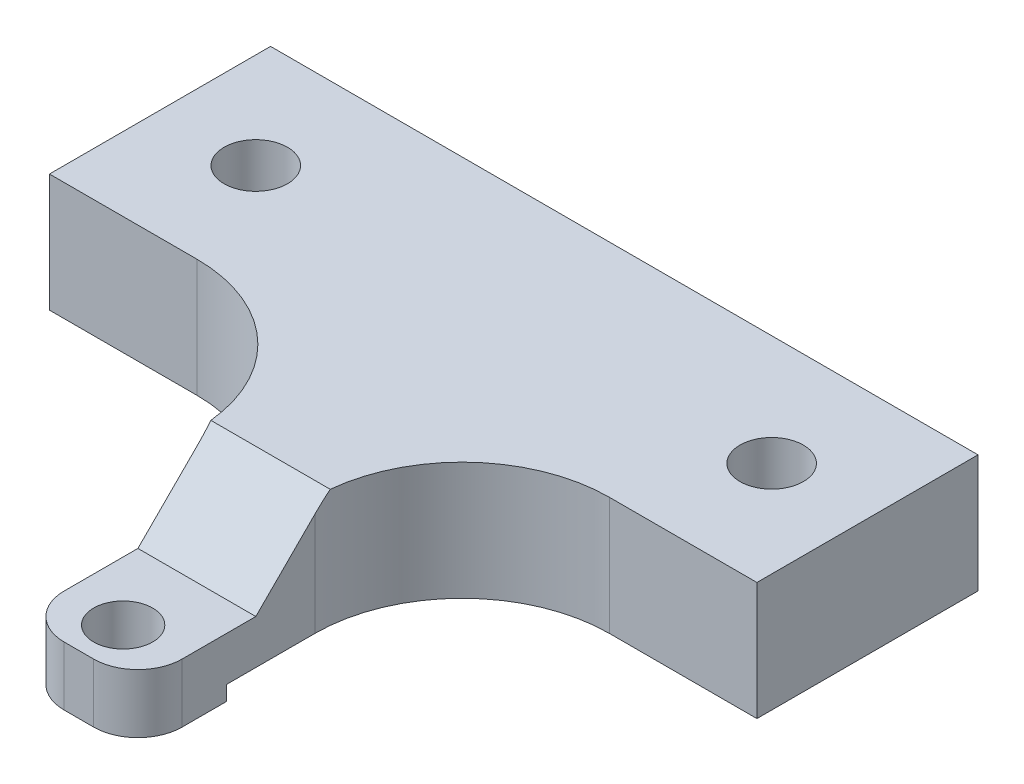
SolidWorks part; units mm, degrees
ref_plane "前视基准面" through (0, 0, 0) normal (0, 0, 1) x (1, 0, 0)
ref_plane "上视基准面" through (0, 0, 0) normal (0, 1, 0) x (1, 0, 0)
ref_plane "右视基准面" through (0, 0, 0) normal (1, 0, 0) x (0, 0, -1)
sketch "草图1" plane through (0, 0, 0) normal (0, 1, 0) x (1, 0, 0)
  line L1 (24, -18.5) -> (-24, -18.5)
  line L2 (24, -18.5) -> (24, 18.5)
  line L3 (24, 18.5) -> (-24, 18.5)
  line L4 (-24, -18.5) -> (-24, 18.5)
  line L5 (24, -18.5) -> (-24, 18.5) construction
  line L6 (24, 18.5) -> (-24, -18.5) construction
  point P0 (0, 0)
  dimension "D1" = 48
  dimension "D2" = 37
extrude "凸台-拉伸1" add sketch "草图1" along normal blind 8
sketch "草图2" plane through (0, 8, 0) normal (0, 1, 0) x (1, 0, 0)
  line L0 (24, 18.5) -> (-24, 18.5) construction
  line L1 (-24, -18.5) -> (-4, -18.5)
  line L2 (-24, -18.5) -> (-24, 3.5)
  line L3 (-24, 3.5) -> (-4, 3.5)
  line L4 (-4, -18.5) -> (-4, 3.5)
  line L5 (0, 0) -> (0, -6.4825) construction
  line L6 (4, -18.5) -> (4, 3.5)
  line L7 (24, 3.5) -> (4, 3.5)
  line L8 (24, -18.5) -> (24, 3.5)
  line L9 (24, -18.5) -> (4, -18.5)
  dimension "D1" = 15
  dimension "D2" = 8
extrude "切除-拉伸1" cut sketch "草图2" against normal through all
fillet "圆角1" radius 10 2 edges at (4, 4, -3.5) (-4, 4, -3.5)
sketch "草图3" plane through (0, 0, 0) normal (0, -1, 0) x (1, 0, 0)
  line L0 (-4, 18.5) -> (-4, 6.5) construction
  line L1 (4, 18.5) -> (-4, 18.5)
  line L2 (4, 18.5) -> (4, 12.5)
  line L3 (4, 12.5) -> (-4, 12.5)
  line L4 (-4, 18.5) -> (-4, 12.5)
  dimension "D1" = 6
extrude "凸台-拉伸2" add sketch "草图3" along normal blind 1
sketch "草图4" plane through (0, 8, 0) normal (0, 1, 0) x (1, 0, 0)
  line L0 (0, -18.5) -> (0, -15.5) construction
  line L1 (-4, -18.5) -> (4, -18.5) construction
  circle A0 centre (0, -15.5) radius 2
  dimension "D1" = 3
extrude "切除-拉伸2" cut sketch "草图4" against normal through all
sketch "草图5" plane through (0, 0, 0) normal (0, -1, 0) x (1, 0, 0)
  line L0 (0, -18.5) -> (0, -11) construction
  line L1 (24, -18.5) -> (-24, -18.5) construction
  line L2 (0, -11) -> (17.5, -11) construction
  circle A0 centre (17.5, -11) radius 2.2811
  circle A1 centre (-17.5, -11) radius 2.2811
  dimension "D1" = 35
  dimension "D2" = 7.5
hole_wizard "M4 六角凹头螺钉的柱形沉头孔1" positions "3D草图1" profile "草图6" counterbore size "M4" standard "Iso" end condition through all
sketch3d "3D草图1"
  point P0 (17.5, 0, -11)
  point P3 (-17.5, 0, -11)
sketch "草图6" plane through (17.5, 0, -11) normal (1, 0, 0) x (0, 0, -1)
  line L0 (0, 0) -> (0, 8)
  line L1 (0, 8) -> (2.15, 8)
  line L3 (2.15, 8) -> (2.15, 4.4)
  line L4 (2.15, 4.4) -> (4, 4.4)
  line L5 (4, 4.4) -> (4, 0)
  line L7 (4, 0) -> (0, 0)
  line L11 (0, -6.35) -> (0, 107.95) construction
  dimension "通孔孔直径" = 4.3
  dimension "通孔孔深度" = 8
  dimension "柱形沉头孔直径" = 8
  dimension "柱形沉头孔深度" = 4.4
sketch "草图7" plane through (0, 8, 0) normal (0, 1, 0) x (1, 0, 0)
  line L0 (4, -6.5) -> (4, -18.5) construction
  line L1 (-4, -18.5) -> (4, -18.5)
  line L2 (-4, -18.5) -> (-4, -10.5)
  line L3 (-4, -10.5) -> (4, -10.5)
  line L4 (4, -18.5) -> (4, -10.5)
  dimension "D1" = 8
extrude "切除-拉伸3" cut sketch "草图7" against normal blind 5
chamfer "倒角1" distance 5 angle 45 1 edges at (0, 8, 10.5)
fillet "圆角2" radius 3 2 edges at (4, 1, 18.5) (-4, 1, 18.5)
